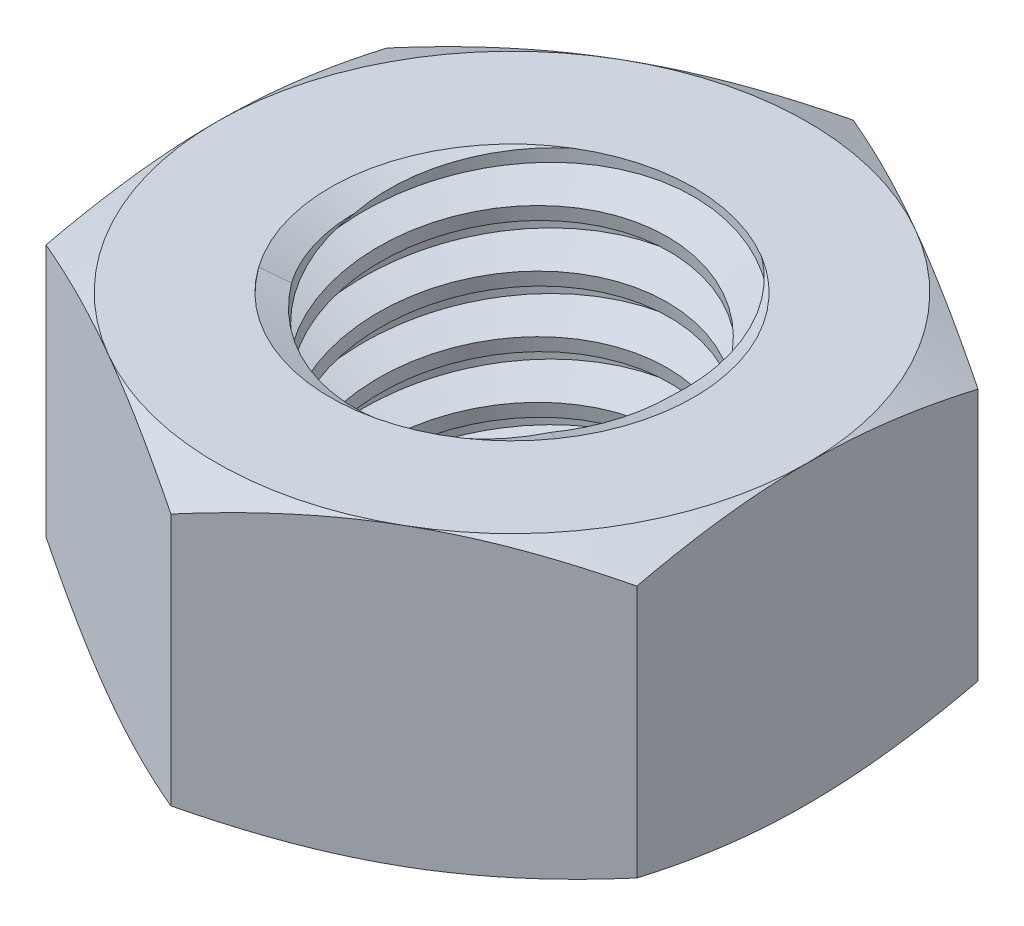
SolidWorks part; units mm, degrees
ref_plane "Front" through (0, 0, 0) normal (0, 0, 1) x (1, 0, 0)
ref_plane "Top" through (0, 0, 0) normal (0, 1, 0) x (1, 0, 0)
ref_plane "Right" through (0, 0, 0) normal (1, 0, 0) x (0, 0, -1)
sketch "Sketch1" plane through (0, 0, 0) normal (0, 1, 0) x (1, 0, 0)
  line L1 (0, 7.5056) -> (-6.5, 3.7528)
  line L2 (-6.5, 3.7528) -> (-6.5, -3.7528)
  line L3 (-6.5, -3.7528) -> (0, -7.5056)
  line L4 (0, -7.5056) -> (6.5, -3.7528)
  line L5 (6.5, -3.7528) -> (6.5, 3.7528)
  line L6 (6.5, 3.7528) -> (0, 7.5056)
  circle A0 centre (0, 0) radius 6.5 construction
  dimension "Hex Flats" = 13
extrude "Extrude1" add sketch "Sketch1" along normal mid plane 6.5
sketch "Sketch2" plane through (0, 0, 0) normal (1, 0, 0) x (0, 0, -1)
  line L0 (-4, -3.25) -> (-4, 3.25) construction
  line L1 (0, -3.25) -> (4, -3.25)
  line L2 (0, -3.25) -> (0, 3.25)
  line L3 (0, 3.25) -> (4, 3.25)
  line L4 (4, -3.25) -> (4, 3.25)
  line L5 (-3.7528, 3.25) -> (3.7528, 3.25) construction
  line L6 (-3.7528, -3.25) -> (3.7528, -3.25) construction
  line L7 (0, -7.25) -> (0, -3.25) construction
  dimension "Thread Dia" = 8
revolve "Revolve1" add sketch "Sketch2" angle 360 about L7
sketch "Sketch3" plane through (0, 0, 0) normal (1, 0, 0) x (0, 0, -1)
  line L0 (4, 3.25) -> (-4, 3.25) construction
  line L1 (-4, 3.25) -> (-4, 2) construction
  line L2 (-4, 2) -> (4, 3.25) construction
  line L3 (4, 3.25) -> (4.0241, 3.0956) construction
  line L4 (4.0241, 3.0956) -> (4.193, 2.015)
  line L5 (4.193, 2.015) -> (3.4642, 2.2965)
  line L6 (3.4642, 2.2965) -> (3.416, 2.6052)
  line L7 (3.416, 2.6052) -> (4.0241, 3.0956)
  line L8 (3.4401, 2.4509) -> (4.1085, 2.5553) construction
  line L9 (4, 3.25) -> (4, 2.5383) construction
  line L10 (4, 2.5383) -> (-4, 1.2883) construction
  line L11 (-4, 1.2883) -> (-4, 2) construction
  line L12 (-0.2089, 3.25) -> (0.2089, 0.5767) construction
  line L13 (-4, -3.25) -> (-4, 3.25) construction
  line L14 (0, 3.25) -> (4, 3.25) construction
  line L15 (4, -3.25) -> (4, 3.25) construction
  line L16 (0, 0) -> (0, 3.25) construction
  line L17 (-4.0241, 3.0956) -> (-4.193, 2.015) construction
  line L18 (-3.416, 2.6052) -> (-4.0241, 3.0956) construction
  line L19 (-3.4642, 2.2965) -> (-3.416, 2.6052) construction
  line L20 (-4.193, 2.015) -> (-3.4642, 2.2965) construction
  line L21 (0.2089, 3.25) -> (-0.2089, 0.5767) construction
  point P13 (0, 1.9133)
  dimension "D1" = 0.1562
  dimension "D2" = 0.3125
  dimension "Thread Pitch" = 1.25
  dimension "D4" = 60
  dimension "D5" = 1.25
revolve "Cut-Revolve1" cut sketch "Sketch3" angle 360 about L12
pattern_linear "LPattern1" count 5 spacing 1.25 along (0, -1, 0) count 2 spacing 1.25 along (0, 1, 0) of "Cut-Revolve1"
sketch "Sketch4" plane through (0, 0, 0) normal (1, 0, 0) x (0, 0, -1)
  line L0 (0, 3.25) -> (4, 3.25)
  line L1 (4, 3.25) -> (3.416, 2.9777)
  line L2 (3.416, 2.9777) -> (3.416, -2.9777)
  line L3 (3.416, -2.9777) -> (4, -3.25)
  line L4 (4, -3.25) -> (0, -3.25)
  line L5 (0, -3.25) -> (0, 3.25)
  line L6 (4, -3.25) -> (4, 3.25) construction
  line L7 (0, 3.25) -> (4, 3.25) construction
  line L8 (0, -3.25) -> (4, -3.25) construction
  line L9 (0, -3.25) -> (0, 3.25) construction
  line L10 (0, 3.25) -> (0, 3.8944) construction
  dimension "D1" = 25
revolve "Cut-Revolve2" cut sketch "Sketch4" angle 360 about L10
combine bodies "Combine1" operation type subtract main body 112 bodies to subtract 111
sketch "Sketch5" plane through (0, 0, 0) normal (1, 0, 0) x (0, 0, -1)
  line L0 (0, -3.25) -> (6.5, -3.25)
  line L1 (6.5, -3.25) -> (7.5056, -2.7811)
  line L2 (7.5056, -2.7811) -> (7.5056, 2.7811)
  line L3 (7.5056, 2.7811) -> (6.5, 3.25)
  line L4 (0, 3.25) -> (0, 4.52)
  line L5 (0, 4.52) -> (8.7756, 4.52)
  line L6 (8.7756, 4.52) -> (8.7756, -4.52)
  line L7 (8.7756, -4.52) -> (0, -4.52)
  line L8 (0, -4.52) -> (0, -3.25)
  line L9 (6.5, 3.25) -> (6.5, -3.25) construction
  line L11 (0, -3.25) -> (4, -3.25) construction
  line L12 (6.5, 3.25) -> (0, 3.25)
  line L13 (7.5056, 0) -> (8.7756, 0) construction
  line L14 (7.5056, 3.25) -> (7.5056, -3.25) construction
  line L15 (0, -3.25) -> (0, 3.25) construction
  line L17 (0, 0) -> (6.5, 0) construction
  line L22 (0, 3.25) -> (4, 3.25) construction
  dimension "D1" = 25
  dimension "D2" = 1.27
  dimension "D3" = 6.5
revolve "Cut-Revolve3" cut sketch "Sketch5" angle 360 about L15
equation "\"D1@Sketch3\"=\"Thread Pitch@Sketch3\"/8"
equation "\"D2@Sketch3\"=\"Thread Pitch@Sketch3\"/4"
equation "\"D5@Sketch3\"=\"Thread Pitch@Sketch3\""
equation "\"D4@LPattern1\"=\"Thread Pitch@Sketch3\""
equation "\"D3@LPattern1\"=\"Thread Pitch@Sketch3\""
equation "\"D1@LPattern1\"=\"Height@Extrude1\"/\"Thread Pitch@Sketch3\""
